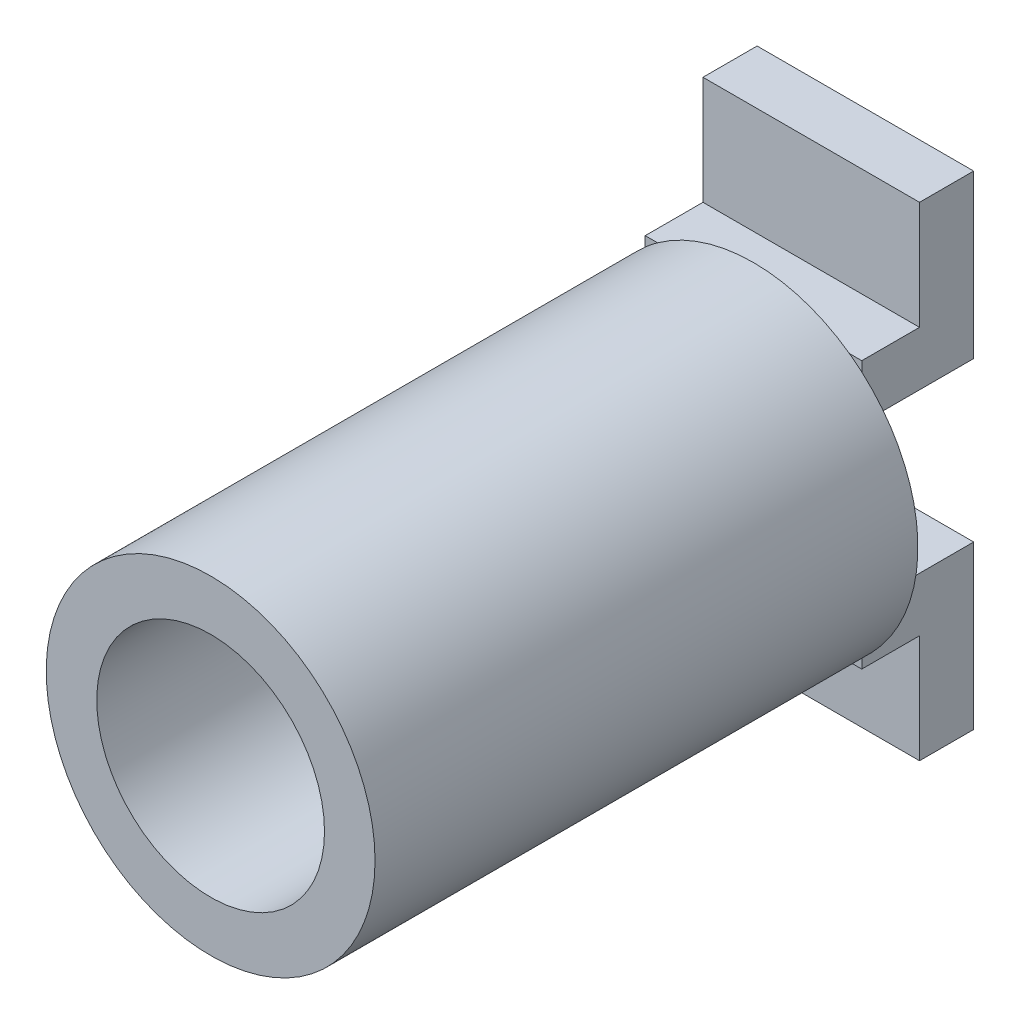
SolidWorks part; units mm, degrees
ref_plane "Front Plane" through (0, 0, 0) normal (0, 0, 1) x (1, 0, 0)
ref_plane "Top Plane" through (0, 0, 0) normal (0, 1, 0) x (1, 0, 0)
ref_plane "Right Plane" through (0, 0, 0) normal (1, 0, 0) x (0, 0, -1)
sketch "Sketch1" plane through (0, 0, 0) normal (0, 0, 1) x (1, 0, 0)
  circle A2 centre (-7.6717, 4.7989) radius 4.555
  circle A4 centre (-7.6717, 4.7989) radius 3.155
  circle A5 centre (-7.6717, 4.7989) radius 3.155
  dimension "D1" = 0.1
extrude "Boss-Extrude1" add sketch "Sketch1" along normal up to surface (7.64 mm away)
sketch "Sketch7" plane through (0, 0, 7.64) normal (0, 0, 1) x (1, 0, 0)
  line L0 (-12.2267, 4.7989) -> (-3.1167, 4.7989) construction
  circle A0 centre (-7.6717, 4.7989) radius 4.555 construction
ref_plane "Plane1" through (0, 4.7989, 0) normal (0, -1, 0) x (1, 0, 0)
sketch "Sketch2" plane through (0, 0, 0) normal (0, 0, -1) x (-1, 0, 0)
  line L4 (10.8417, 5.2839) -> (4.5017, 5.2839)
  line L5 (4.5017, 5.2839) -> (4.5017, 3.5839)
  line L6 (4.5017, 3.5839) -> (10.8417, 3.5839)
  line L7 (10.8417, 3.5839) -> (10.8417, 5.2839)
  line L8 (10.8417, 5.2839) -> (4.5017, 5.2839)
  line L9 (4.5017, 5.2839) -> (4.5017, 3.5839)
  line L10 (4.5017, 3.5839) -> (10.8417, 3.5839)
  line L11 (10.8417, 3.5839) -> (10.8417, 5.2839)
  circle A0 centre (7.6717, 4.7989) radius 3.155 construction
  circle A1 centre (7.6717, 4.7989) radius 3.155
  circle M5 centre (7.6717, 4.7989) radius 4.555
  circle M6 centre (7.6717, 4.7989) radius 3.155
  dimension "D1" = 0
extrude "Boss-Extrude2" add sketch "Sketch2" along normal up to surface (5.9 mm away) contours L11 L10 L9 L8 M5 M6 region at (-3.2455, 4.7989, 0)
sketch "Sketch3" plane through (0, 0, -5.9) normal (0, 0, -1) x (-1, 0, 0)
  line L0 (7.6717, 7.7989) -> (7.6717, 1.7989) construction
  line L1 (7.6717, 9.3539) -> (7.6717, 0.2439)
  circle A0 centre (7.6717, 4.7989) radius 4.555 construction
  circle A1 centre (7.6717, 4.7989) radius 4.555
  line M1 (10.8417, 5.2839) -> (10.8417, 3.5839)
  line M2 (10.8417, 3.5839) -> (10.5834, 3.5839)
  arc M3 (10.5834, 3.5839) -> (4.76, 3.5839) centre (7.6717, 4.7989) cw
  line M4 (4.76, 3.5839) -> (4.5017, 3.5839)
  line M5 (4.5017, 3.5839) -> (4.5017, 5.2839)
  line M6 (4.5017, 5.2839) -> (4.5542, 5.2839)
  arc M7 (4.5542, 5.2839) -> (10.7892, 5.2839) centre (7.6717, 4.7989) cw
  line M8 (10.7892, 5.2839) -> (10.8417, 5.2839)
  circle M9 centre (7.6717, 4.7989) radius 4.555
extrude "Boss-Extrude3" add sketch "Sketch3" along normal blind 1.5 contours L1 M9 M7 M8 M1 M2 M3 | L1 M7 M3 M2 M1 M8 | L1 M9 M3 M4 M5 M6 M7 region at (-10.8206, 7.9477, -5.9) region at (-7.5699, 8.6539, -5.9) region at (-9.0251, 4.7928, -5.9)
sketch "Sketch4" plane through (0, 0, -7.4) normal (0, 0, -1) x (-1, 0, 0)
  line L0 (10.6717, 4.7989) -> (4.6717, 4.7989) construction
  line L1 (7.6717, 8.4989) -> (10.6717, 8.4989)
  line L2 (7.6717, 8.4989) -> (7.6717, 1.0989)
  line L3 (7.6717, 1.0989) -> (10.6717, 1.0989)
  line L4 (10.6717, 8.4989) -> (10.6717, 1.0989)
  line L5 (7.6717, 8.4989) -> (10.6717, 1.0989) construction
  line L6 (7.6717, 1.0989) -> (10.6717, 8.4989) construction
  line L7 (7.6717, 7.9539) -> (7.6717, 1.6439) construction
  line L8 (6.1717, 6.9989) -> (6.1717, 8.4989) construction
  line L9 (4.6717, 8.4989) -> (7.6717, 8.4989)
  line L10 (4.6717, 8.4989) -> (4.6717, 1.0989)
  line L11 (4.6717, 1.0989) -> (7.6717, 1.0989)
  line L12 (7.6717, 8.4989) -> (7.6717, 1.0989)
  line L13 (4.6717, 8.4989) -> (7.6717, 1.0989) construction
  line L14 (4.6717, 1.0989) -> (7.6717, 8.4989) construction
  line L15 (10.6717, 8.4989) -> (12.1717, 8.4989)
  line L16 (10.6717, 8.4989) -> (10.6717, 6.4989)
  line L17 (10.6717, 6.4989) -> (12.1717, 6.4989)
  line L18 (12.1717, 8.4989) -> (12.1717, 6.4989)
  line L19 (10.6717, 1.0989) -> (12.1717, 1.0989)
  line L20 (10.6717, 1.0989) -> (10.6717, 3.0989)
  line L21 (10.6717, 3.0989) -> (12.1717, 3.0989)
  line L22 (12.1717, 1.0989) -> (12.1717, 3.0989)
  line L23 (4.6717, 1.0989) -> (3.1717, 1.0989)
  line L24 (4.6717, 1.0989) -> (4.6717, 3.0989)
  line L25 (4.6717, 3.0989) -> (3.1717, 3.0989)
  line L26 (3.1717, 1.0989) -> (3.1717, 3.0989)
  line L27 (4.6717, 8.4989) -> (3.1717, 8.4989)
  line L28 (4.6717, 8.4989) -> (4.6717, 6.4989)
  line L29 (4.6717, 6.4989) -> (3.1717, 6.4989)
  line L30 (3.1717, 8.4989) -> (3.1717, 6.4989)
  line L31 (4.6717, 1.0989) -> (7.6717, 1.0989)
  line L32 (4.6717, 1.0989) -> (4.6717, 2.5989)
  line L33 (4.6717, 2.5989) -> (7.6717, 2.5989)
  line L34 (7.6717, 1.0989) -> (7.6717, 2.5989)
  line L35 (4.6717, 8.4989) -> (7.6717, 8.4989)
  line L36 (4.6717, 8.4989) -> (4.6717, 6.9989)
  line L37 (4.6717, 6.9989) -> (7.6717, 6.9989)
  line L38 (7.6717, 8.4989) -> (7.6717, 6.9989)
  line L39 (6.1717, 2.5989) -> (6.1717, 1.0989) construction
  point P0 (9.1717, 4.7989)
  point P9 (6.1717, 4.7989)
  circle M18 centre (7.6717, 4.7989) radius 4.555
  line M19 (7.6717, 7.9539) -> (7.6717, 1.6439)
  arc M44 (4.5542, 5.2839) -> (7.6717, 7.9539) centre (7.6717, 4.7989) cw
  arc M45 (7.6717, 1.6439) -> (4.76, 3.5839) centre (7.6717, 4.7989) cw
  dimension "D1" = 3
  dimension "D2" = 7.4
  dimension "D3" = 3.4
  dimension "D4" = 1.5
extrude "Boss-Extrude4" add sketch "Sketch4" along normal blind 3.1 contours L4 L1 L12 L3 M18 M19 | L10 L37 L9 M19 | L33 L24 L11 L12 | L4 L1 M18 | L4 L3 M18 | L9 L10 M18 | L10 L11 M18 | L33 L12 M45 | L37 M44 M19 region at (-9.166, 4.7989, -7.4) region at (-5.8754, 7.921, -7.4) region at (-10.5592, 8.4096, -7.4) region at (-6.8035, 7.3863, -7.4) region at (-4.7842, 8.4096, -7.4) region at (-6.8035, 2.2115, -7.4) region at (-5.8754, 1.6768, -7.4) region at (-10.5592, 1.1882, -7.4) region at (-4.7842, 1.1882, -7.4)
sketch "Sketch5" plane through (0, 8.4989, 0) normal (0, 1, 0) x (1, 0, 0)
  line L0 (-10.6717, 10.5) -> (-10.6717, 7.4) construction
  line L1 (-10.6717, 9) -> (-4.6717, 9)
  line L2 (-10.6717, 9) -> (-10.6717, 10.5)
  line L3 (-10.6717, 10.5) -> (-4.6717, 10.5)
  line L4 (-4.6717, 9) -> (-4.6717, 10.5)
  point P6 (0, 0)
  dimension "D1" = 1.5
extrude "Boss-Extrude5" add sketch "Sketch5" along normal blind 3
mirror "Mirror1" about plane through (0, 4.7989, 0) normal (0, -1, 0) of "Boss-Extrude5"
equation "\"D3@Sketch4\"=3.00mm+.2*2"
